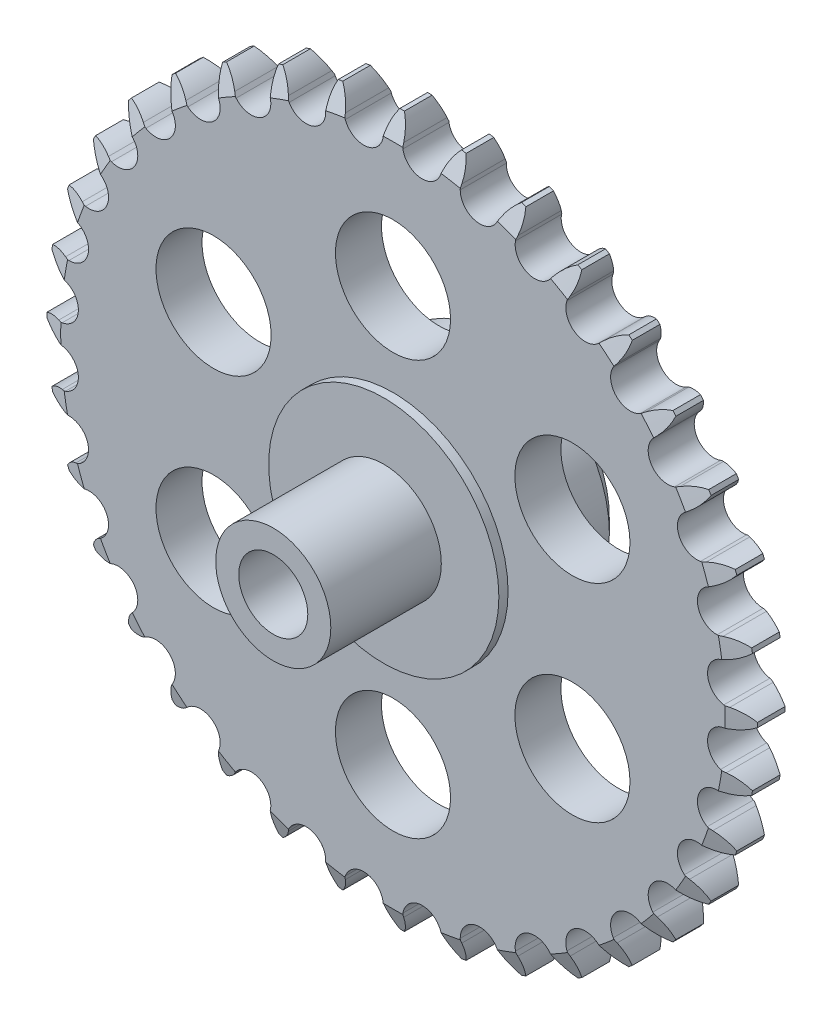
SolidWorks part; units mm, degrees
material "AISI 304"
ref_plane "Front Plane" through (0, 0, 0) normal (0, 0, 1) x (1, 0, 0)
ref_plane "Top Plane" through (0, 0, 0) normal (0, 1, 0) x (1, 0, 0)
ref_plane "Right Plane" through (0, 0, 0) normal (1, 0, 0) x (0, 0, -1)
ref_axis "Axis1" through (0, 0, -22.55) along (0, 0, 1)
sketch "Sketch1" plane through (0, 0, 0) normal (0, 0, 1) x (1, 0, 0)
  line L0 (0, 0) -> (0, 72.8581) construction
  line L1 (-2.1568, 71.8581) -> (2.1568, 71.8581) construction
  line L2 (-2.1568, 71.8581) -> (-2.0429, 72.8581) construction
  line L3 (2.1568, 71.8581) -> (2.0429, 72.8581) construction
  line L4 (-2.0429, 72.8581) -> (2.0429, 72.8581) construction
  line L7 (-0.5, 77.163) -> (0.5, 77.163) construction
  circle A0 centre (0, 0) radius 72.8581 construction
  circle A1 centre (6.35, 72.5808) radius 4.255 construction
  circle A2 centre (-6.35, 72.5808) radius 4.255 construction
  circle A3 centre (0, 0) radius 68.6031 construction
  arc A4 (-2.0429, 72.8581) -> (-0.5, 77.163) centre (7.8928, 71.726) cw construction
  arc A5 (2.0429, 72.8581) -> (0.5, 77.163) centre (-7.8928, 71.726) ccw construction
  dimension "RollerDia" = 8.51
  dimension "D4" = 10
  dimension "D1" = 13
  dimension "D2" = 1
  dimension "D3" = 1
  dimension "D5" = 1
sketch "Sketch2" plane through (0, 0, 0) normal (0, 0, 1) x (1, 0, 0)
  circle A0 centre (0, 0) radius 68.6031 construction
  circle A1 centre (0, 0) radius 68.6031
extrude "Boss-Extrude1" add sketch "Sketch2" along normal mid plane 10
sketch "Sketch4" plane through (0, 0, 0) normal (0, 0, 1) x (1, 0, 0)
  line L0 (-0.5, 77.163) -> (0.5, 77.163) construction
  line L1 (-2.1568, 71.8581) -> (-2.0429, 72.8581) construction
  line L2 (2.1568, 71.8581) -> (2.0429, 72.8581) construction
  line L3 (-0.5, 77.163) -> (0.5, 77.163)
  line L4 (-2.1568, 71.8581) -> (-2.0429, 72.8581)
  line L5 (2.1568, 71.8581) -> (2.0429, 72.8581)
  circle A0 centre (0, 0) radius 68.6031 construction
  circle A1 centre (6.35, 72.5808) radius 4.255 construction
  circle A2 centre (-6.35, 72.5808) radius 4.255 construction
  arc A3 (2.0429, 72.8581) -> (0.5, 77.163) centre (-7.8928, 71.726) ccw construction
  arc A4 (-0.5, 77.163) -> (-2.0429, 72.8581) centre (7.8928, 71.726) ccw construction
  arc A5 (5.9792, 68.342) -> (-5.9792, 68.342) centre (0, 0) ccw
  arc A6 (2.1568, 71.8581) -> (5.9792, 68.342) centre (6.35, 72.5808) ccw
  arc A7 (-5.9792, 68.342) -> (-2.1568, 71.8581) centre (-6.35, 72.5808) ccw
  arc A8 (2.0429, 72.8581) -> (0.5, 77.163) centre (-7.8928, 71.726) ccw
  arc A9 (-0.5, 77.163) -> (-2.0429, 72.8581) centre (7.8928, 71.726) ccw
extrude "Boss-Extrude2" add sketch "Sketch4" along normal up to surface and the other way up to surface up to face at (68.6031, 0, 5) other way up to face at (68.6031, 0, -5)
pattern_circular "CirPattern1" count 36 over 360 about axis through (0, 0, 5) along (0, 0, -1) of "Boss-Extrude2"
sketch "Sketch5" plane through (0, 0, 0) normal (1, 0, 0) x (0, 0, -1)
  line L0 (0, 0) -> (-6, 0) construction
  line L1 (0, 77.163) -> (0, 72.8581) construction
  line L2 (-6, 84.663) -> (6, 84.663)
  line L3 (-6, 84.663) -> (-6, 69.663)
  line L4 (-6, 69.663) -> (6, 69.663) construction
  line L5 (6, 84.663) -> (6, 69.663)
  line L6 (-6, 84.663) -> (6, 69.663) construction
  line L7 (-6, 69.663) -> (6, 84.663) construction
  line L8 (-6, 69.663) -> (0, 84.663)
  line L9 (6, 69.663) -> (0, 84.663)
  line L10 (0, 77.163) -> (0, 72.8581) construction
  point P1 (0, 77.163)
  dimension "D1" = 15
  dimension "D2" = 1
revolve "Cut-Revolve7" cut sketch "Sketch5" angle 360 about L0 region at (0, 79.663, -4) region at (0, 79.663, 4)
sketch "Sketch6" plane through (0, 0, 0) normal (0, 0, 1) x (1, 0, 0)
  circle A0 centre (0, 0) radius 25
  dimension "D1" = 50
extrude "Boss-Extrude3" add sketch "Sketch6" along normal blind 7 and the other way blind 20
sketch "Sketch7" plane through (0, 0, 0) normal (0, 0, 1) x (1, 0, 0)
  circle A0 centre (0, 0) radius 7.5
  dimension "D1" = 15
extrude "Cut-Extrude1" cut sketch "Sketch7" against normal through all both and the other way through all
sketch "Sketch9" plane through (0, 0, 7) normal (0, 0, 1) x (1, 0, 0)
  circle A2 centre (0, 0) radius 12.5
  circle A3 centre (0, 0) radius 12.5
  circle M2 centre (0, 0) radius 7.5
  dimension "D1" = 5
extrude "Boss-Extrude4" add sketch "Sketch9" along normal blind 24 contours A3 M2 region at (-12.1464, 0, 7)
sketch "Sketch8" plane through (0, 0, 0) normal (0, 0, 1) x (1, 0, 0)
  circle A0 centre (0, 45) radius 12.5
  dimension "D2" = 25
  dimension "D1" = 45
extrude "Cut-Extrude2" cut sketch "Sketch8" against normal through all both and the other way through all
pattern_circular "CirPattern2" count 6 over 360 about axis through (0, 0, 6) along (0, 0, 1) of "Cut-Extrude2"
chamfer "Chamfer1" distance 3 angle 45 1 edges at (25, 0, -20)
sketch "Sketch10" plane through (0, 0, -20) normal (0, 0, -1) x (-1, 0, 0)
  line L0 (14.046, -3.7902) -> (29.0062, -2.4814)
  line L4 (29.0062, -2.4814) -> (28.1346, 7.4806)
  line L7 (14.4955, -1.24) -> (29.0062, -2.4814) construction
  line L8 (14.0599, 3.7383) -> (28.1346, 7.4806) construction
  line L9 (13.1745, 6.1717) -> (28.1346, 7.4806)
  arc A0 (14.046, -3.7902) -> (13.1745, 6.1717) centre (0, 0) ccw
  point P0 (0, 0)
  dimension "D1" = 10
extrude "Cut-Extrude5" cut sketch "Sketch10" against normal blind 3
equation "\"ChainPitch\"=12.7"
equation "\"ChainPitch@Sketch1\"=\"ChainPitch\""
equation "\"SprocketPitchDiameter@Sketch1\" = \"ChainPitch\" / sin ( 180 / \"NumberOfTeeth\" )"
equation "\"NumberOfTeeth\"= 36"
equation "\"D1@CirPattern1\"=\"NumberOfTeeth\""
